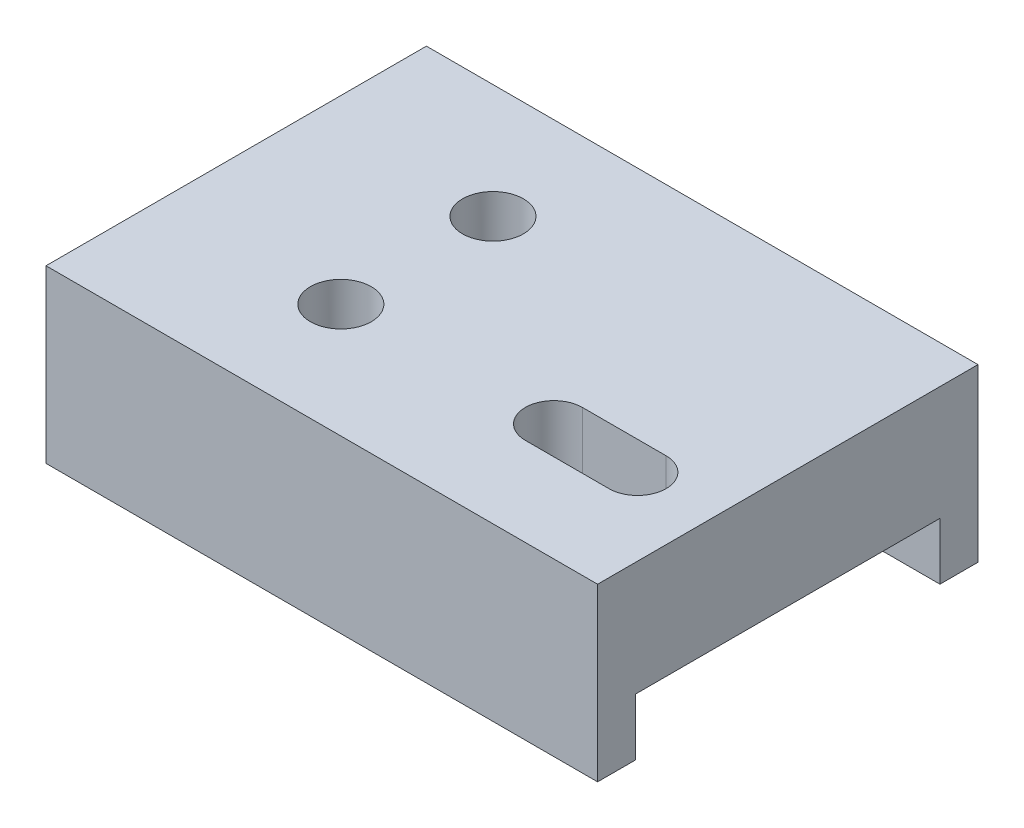
SolidWorks part; units mm, degrees
material "ABS"
ref_plane "Front" through (0, 0, 0) normal (0, 0, 1) x (1, 0, 0)
ref_plane "Top" through (0, 0, 0) normal (0, 1, 0) x (1, 0, 0)
ref_plane "Right" through (0, 0, 0) normal (1, 0, 0) x (0, 0, -1)
sketch "Esquisse1" plane through (0, 0, 0) normal (1, 0, 0) x (0, 0, -1)
  line L0 (20, 0) -> (0, 0)
  line L1 (0, 0) -> (0, -14)
  dimension "D1" = 90
  dimension "D2" = 20
  dimension "D3" = 14
extrude "Extru.-Mince1" add sketch "Esquisse1" along normal mid plane 19 thin thin type one direction reverse wall 6
fillet "Congé2" [suppressed] radius 2
sketch "Esquisse2" plane through (0, 0, 0) normal (0, 1, 0) x (1, 0, 0)
  line L1 (9.5, 0) -> (-9.5, 0) construction
  circle A1 centre (0, 14) radius 1.6
  dimension "D2" = 14
  dimension "D3" = 3.2
extrude "Enlèv. mat.-Extru.1" cut sketch "Esquisse2" against normal through all
sketch "Esquisse3" plane through (0, 0, 0) normal (0, 0, 1) x (1, 0, 0)
  line L0 (9.5, -14) -> (-9.5, -14) construction
  line L2 (9.5, 0) -> (-9.5, 0) construction
  circle A0 centre (0, -9) radius 1.6
  dimension "D1" = 5
  dimension "D2" = 3.2
  dimension "D3" = 9
extrude "Enlèv. mat.-Extru.2" [suppressed] cut sketch "Esquisse3" against normal through all
sketch "Esquisse4" plane through (0, 0, 0) normal (0, 1, 0) x (1, 0, 0)
  circle A0 centre (0, 14) radius 3
  circle A1 centre (0, 14) radius 1.6 construction
  dimension "D1" = 6
extrude "Enlèv. mat.-Extru.3" cut sketch "Esquisse4" against normal through all from offset 2.5 offset against normal yes
sketch "Esquisse5" [suppressed] plane through (0, 0, 0) normal (0, 0, 1) x (1, 0, 0)
  line L13 (-1.5877, -6.25) -> (-3.1754, -9)
  line L14 (-3.1754, -9) -> (-1.5877, -11.75)
  line L15 (-1.5877, -11.75) -> (1.5877, -11.75)
  line L16 (1.5877, -11.75) -> (3.1754, -9)
  line L17 (3.1754, -9) -> (1.5877, -6.25)
  line L18 (1.5877, -6.25) -> (-1.5877, -6.25)
  circle A3 centre (0, -9) radius 2.75 construction
  dimension "D1" = 5.5
extrude "Enlèv. mat.-Extru.4" [suppressed] cut sketch "Esquisse5" against normal blind 8 from offset 3 offset against normal yes
fillet "Congé1" [suppressed] radius 5
sketch "Esquisse6" plane through (0, 0, 0) normal (0, 1, 0) x (1, 0, 0)
  line L0 (9.5, 20) -> (-9.5, 20) construction
  line L1 (-2.35, 20) -> (2.35, 20)
  line L2 (-2.35, 20) -> (-2.35, 0)
  line L3 (-2.35, 0) -> (2.35, 0)
  line L4 (2.35, 20) -> (2.35, 0)
  circle A0 centre (0, 14) radius 1.6 construction
  circle A1 centre (0, 14) radius 1.6
  dimension "D1" = 4.7
extrude "Boss.-Extru.1" [suppressed] add sketch "Esquisse6" along normal blind 1.5
fillet "Congé3" [suppressed] radius 0.5
sketch "Esquisse7" [suppressed] plane through (0, 0, 0) normal (0, 0, 1) x (1, 0, 0)
  circle A1 centre (0, -9) radius 1.6 construction
  circle A2 centre (0, -9) radius 1.6
extrude "Boss.-Extru.2" [suppressed] add sketch "Esquisse7" against normal blind 0.2
sketch "Sketch1" [suppressed] plane through (0, 0, -15) normal (0, 0, -1) x (-1, 0, 0)
  line L1 (-2.35, 0) -> (3.0183, 0)
  line L2 (-2.35, 0) -> (-2.35, 3.1233)
  line L3 (-2.35, 3.1233) -> (3.0183, 3.1233)
  line L4 (3.0183, 0) -> (3.0183, 3.1233)
extrude "Cut-Extrude1" [suppressed] cut sketch "Sketch1" against normal through all
sketch "Sketch2" plane through (0, 0, -6) normal (0, 0, -1) x (-1, 0, 0)
  line L1 (-9.5, -6) -> (9.5, -6)
  line L2 (-9.5, -6) -> (-9.5, -14)
  line L3 (-9.5, -14) -> (9.5, -14)
  line L4 (9.5, -6) -> (9.5, -14)
extrude "Cut-Extrude2" cut sketch "Sketch2" against normal through all
sketch "Sketch4" plane through (0, -6, 0) normal (0, -1, 0) x (1, 0, 0)
  line L0 (9.5, -20) -> (9.5, 0) construction
  line L1 (-9.5, 0) -> (9.5, 0)
  line L2 (-9.5, 0) -> (-9.5, -2)
  line L3 (-9.5, -2) -> (9.5, -2)
  line L4 (9.5, 0) -> (9.5, -2)
  line L6 (-9.5, -20) -> (9.5, -20)
  line L7 (-9.5, -20) -> (-9.5, -18)
  line L8 (-9.5, -18) -> (9.5, -18)
  line L9 (9.5, -20) -> (9.5, -18)
  dimension "D1" = 2
extrude "Boss-Extrude2" add sketch "Sketch4" along normal blind 3
sketch "Sketch5" plane through (9.5, 0, 0) normal (1, 0, 0) x (0, 0, -1)
  line L8 (0, 0) -> (0, -9)
  line L9 (0, -9) -> (2, -9)
  line L10 (2, -9) -> (2, -6)
  line L11 (2, -6) -> (18, -6)
  line L12 (18, -6) -> (18, -9)
  line L13 (18, -9) -> (20, -9)
  line L14 (20, -9) -> (20, 0)
  line L15 (20, 0) -> (0, 0)
  line L16 (0, 0) -> (0, -9)
  line L17 (0, -9) -> (2, -9)
  line L18 (2, -9) -> (2, -6)
  line L19 (2, -6) -> (18, -6)
  line L20 (18, -6) -> (18, -9)
  line L21 (18, -9) -> (20, -9)
  line L22 (20, -9) -> (20, 0)
  line L23 (20, 0) -> (0, 0)
  dimension "D1" = 0
extrude "Boss-Extrude3" add sketch "Sketch5" along normal blind 10
sketch "Sketch6" plane through (0, -6, 0) normal (0, -1, 0) x (1, 0, 0)
  circle A0 centre (11.05, -6.15) radius 1.5
  dimension "D1" = 3
extrude "Cut-Extrude3" cut sketch "Sketch6" against normal through all
sketch "Sketch7" plane through (0, -6, 0) normal (0, -1, 0) x (1, 0, 0)
  line L0 (11.05, -6.15) -> (15.4501, -6.15) construction
  line L1 (11.05, -4.65) -> (15.4501, -4.65)
  line L2 (11.05, -7.65) -> (15.4501, -7.65)
  circle A0 centre (11.05, -6.15) radius 1.5 construction
  arc A1 (11.05, -7.65) -> (11.05, -4.65) centre (11.05, -6.15) ccw
  arc A3 (15.4501, -7.65) -> (15.4501, -4.65) centre (15.4501, -6.15) ccw
  point P2 (15.4501, -6.15)
  point P3 (14.275, -6.15)
extrude "Cut-Extrude6" cut sketch "Sketch7" against normal through all
pattern_linear "LPattern1" count 2 spacing 8 along (0, 0, 1) of "Enlèv. mat.-Extru.1", "Enlèv. mat.-Extru.3"
